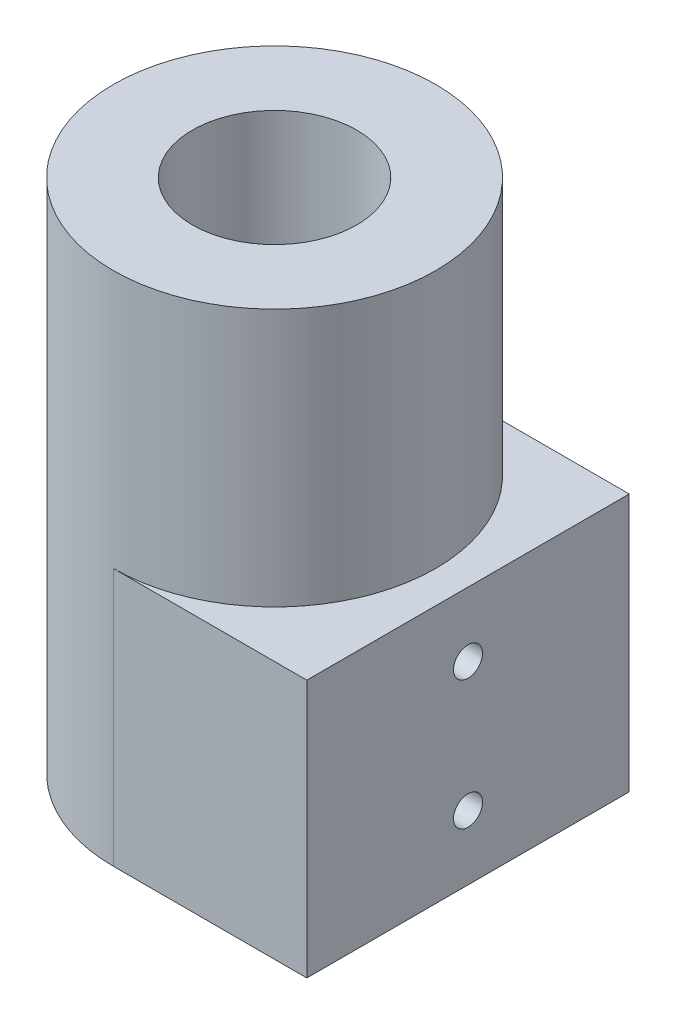
SolidWorks part; units mm, degrees
ref_plane "Front Plane" through (0, 0, 0) normal (0, 0, 1) x (1, 0, 0)
ref_plane "Top Plane" through (0, 0, 0) normal (0, 1, 0) x (1, 0, 0)
ref_plane "Right Plane" through (0, 0, 0) normal (1, 0, 0) x (0, 0, -1)
sketch "Sketch1" plane through (0, 0, 0) normal (0, 1, 0) x (1, 0, 0)
  circle A0 centre (0, 0) radius 25
  dimension "D1" = 50
extrude "Boss-Extrude1" add sketch "Sketch1" along normal blind 80
sketch "Sketch2" plane through (0, 80, 0) normal (0, 1, 0) x (1, 0, 0)
  circle A0 centre (0, 0) radius 12.75
  dimension "D1" = 25.5
extrude "Cut-Extrude1" cut sketch "Sketch2" against normal through all
sketch "Sketch3" plane through (0, 0, 0) normal (1, 0, 0) x (0, 0, -1)
  line L0 (0, 30) -> (0, 10) construction
  line L1 (-25, 0) -> (25, 0) construction
  line L2 (0, 0) -> (0, 20) construction
  circle A0 centre (0, 30) radius 1.4
  circle A1 centre (0, 10) radius 1.4
  dimension "D3" = 2.8
  dimension "D1" = 20
  dimension "D2" = 10
extrude "Cut-Extrude2" cut sketch "Sketch3" against normal through all
ref_plane "Plane1" through (25, 0, 0) normal (1, 0, 0) x (0, 0, -1)
sketch "Sketch5" plane through (25, 0, 0) normal (1, 0, 0) x (0, 0, -1)
  line L0 (25, 0) -> (-25, 0) construction
  line L2 (25, 0) -> (-25, 0)
  line L3 (25, 0) -> (25, 40)
  line L4 (25, 40) -> (-25, 40)
  line L5 (-25, 0) -> (-25, 40)
  line L6 (25, 0) -> (-25, 40) construction
  line L7 (25, 40) -> (-25, 0) construction
  point P4 (0, 0)
  point P7 (0, 20)
  dimension "D1" = 50
  dimension "D2" = 40
extrude "Boss-Extrude2" add sketch "Sketch5" against normal up to surface and the other way blind 5 up to face at (-24.998, 31.363, 0.3195)
sketch "Sketch6" plane through (30, 0, 0) normal (1, 0, 0) x (0, 0, -1)
  line L0 (0, 0) -> (0, 40) construction
  line L1 (-25, 0) -> (25, 0) construction
  line L2 (25, 40) -> (-25, 40) construction
  circle A0 centre (0, 10) radius 2.25
  circle A1 centre (0, 30) radius 2.25
  dimension "D1" = 4.5
  dimension "D2" = 10
  dimension "D3" = 10
extrude "Cut-Extrude3" cut sketch "Sketch6" against normal blind 10
